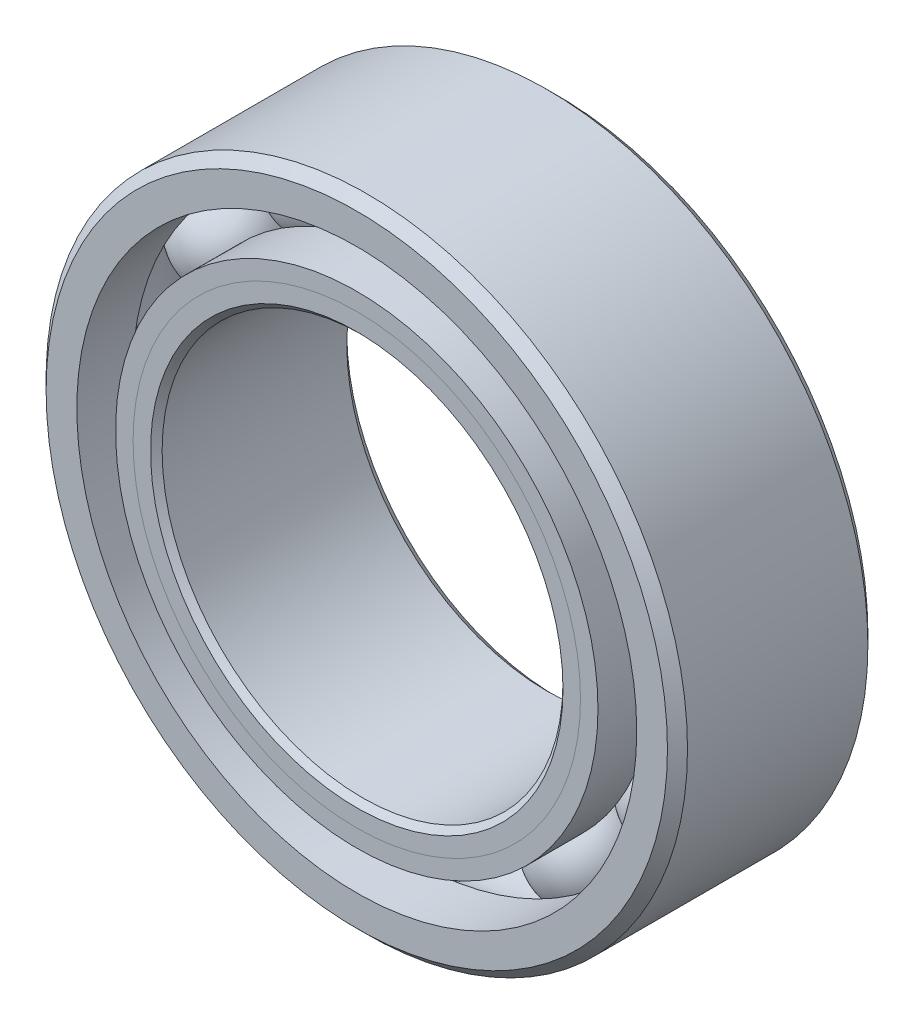
SolidWorks part; units mm, degrees
ref_plane "Front Plane" through (0, 0, 0) normal (0, 0, 1) x (1, 0, 0)
ref_plane "Top Plane" through (0, 0, 0) normal (0, 1, 0) x (1, 0, 0)
ref_plane "Right Plane" through (0, 0, 0) normal (1, 0, 0) x (0, 0, -1)
sketch "Sketch1" plane through (0, 0, 0) normal (1, 0, 0) x (0, 0, -1)
  line L0 (-1.9844, 0) -> (1.9844, 0) construction
  line L1 (0, 6.35) -> (0, -6.35) construction
  line L2 (1.7859, 6.35) -> (-1.7859, 6.35)
  line L3 (-1.7859, 6.35) -> (-1.9844, 6.1516)
  line L4 (-1.9844, 6.1516) -> (-1.9844, 5.5432)
  line L5 (-1.9844, 5.5432) -> (-0.8819, 5.5432)
  line L6 (1.9844, 5.5432) -> (0.8819, 5.5432)
  line L7 (1.9844, 6.1516) -> (1.9844, 5.5432)
  line L8 (1.7859, 6.35) -> (1.9844, 6.1516)
  line L9 (0, 6.35) -> (0, 5.1594) construction
  line L10 (0, 5.1594) -> (0, 3.9688) construction
  arc A0 (-0.8819, 5.5432) -> (0.8819, 5.5432) centre (0, 5.1594) cw
  point P14 (0, 3.9688)
  dimension "Width" = 3.9688
  dimension "OD" = 12.7
  dimension "D1" = 45
  dimension "D2" = 0.1984
  dimension "D3" = 1.7639
  dimension "D4" = 0.3838
revolve "Revolve1" add sketch "Sketch1" angle 360 about L0
sketch "Sketch2" plane through (0, 0, 0) normal (1, 0, 0) x (0, 0, -1)
  line L0 (-1.9844, 4.7756) -> (-0.8819, 4.7756)
  line L1 (-1.9844, 6.1516) -> (-1.9844, -6.1516) construction
  line L2 (-1.9844, 4.7756) -> (-1.9844, 4.4294)
  line L3 (-1.9844, 4.4294) -> (-1.6382, 4.0831)
  line L4 (-1.6382, 4.0831) -> (0, 4.0831)
  line L5 (0, 6.35) -> (0, -6.35) construction
  line L6 (0, 4.0831) -> (0, 4.1975)
  line L7 (0, 4.1975) -> (0, 3.9688) construction
  line L8 (-1.9844, 4.7756) -> (-1.9844, 4.0831) construction
  line L9 (-1.9844, 4.0831) -> (-1.6382, 4.0831) construction
  arc A0 (-0.8819, 4.7756) -> (0, 4.1975) centre (0, 5.1594) ccw
  arc A1 (0.8819, 5.5432) -> (-0.8819, 5.5432) centre (0, 5.1594) ccw construction
  circle A2 centre (0, 5.1594) radius 0.9618 construction
  dimension "D1" = 45
revolve "Revolve2" add sketch "Sketch2" angle 360 about L0
sketch "Sketch3" plane through (0, 0, 0) normal (1, 0, 0) x (0, 0, -1)
  line L0 (-1.9844, 4.4294) -> (-1.6382, 4.0831)
  line L1 (-1.6382, 4.0831) -> (0, 4.0831)
  line L2 (0, 4.0831) -> (0, 4.1975)
  line L3 (-1.9844, 4.4294) -> (-1.9844, 4.0831)
  line L4 (-1.9844, 4.7756) -> (-1.9844, 4.0831) construction
  line L5 (-1.9844, 4.0831) -> (-1.87, 3.9688)
  line L6 (-1.87, 3.9688) -> (1.7859, 3.9688)
  line L7 (1.7859, 6.35) -> (1.7859, -6.35) construction
  line L8 (1.7859, 3.9688) -> (1.9844, 4.1672)
  line L9 (1.9844, -6.1516) -> (1.9844, 6.1516) construction
  line L10 (1.9844, 4.1672) -> (1.9844, 4.7756)
  line L11 (1.9844, 4.7756) -> (0.8819, 4.7756)
  line L13 (1.7859, 6.35) -> (1.9844, 6.1516) construction
  circle A0 centre (0, 5.1594) radius 0.9618 construction
  arc A1 (0.8819, 4.7756) -> (0, 4.1975) centre (0, 5.1594) cw
revolve "Revolve3" add sketch "Sketch3" angle 360 about L0
sketch "Sketch4" plane through (0, 0, 0) normal (1, 0, 0) x (0, 0, -1)
  line L0 (-0.9618, 5.1594) -> (0.9618, 5.1594)
  circle A1 centre (0, 5.1594) radius 0.9618 construction
  arc A2 (-0.9618, 5.1594) -> (0.9618, 5.1594) centre (0, 5.1594) cw
  arc A3 (0.8819, 5.5432) -> (-0.8819, 5.5432) centre (0, 5.1594) ccw construction
revolve "Revolve4" add sketch "Sketch4" angle 360 about L0
ref_axis "Axis1" through (0, 0, -1.9844) along (0, 0, 1)
pattern_circular "CirPattern1" count 12 every 30 about axis through (0, 0, -1.9844) along (0, 0, 1) of bodies 104
equation "\"D2@Sketch1\" = \"Width@Sketch1\"*.05"
equation "\"D3@Sketch1\" = \"Width@Sketch1\"/2.25"
equation "\"D4@Sketch1\" = (((\"OD@Sketch1\"-\"Width@Sketch1\")/2)/3.25)/3.5"
equation "\"D2@CirPattern1\" = 360/\"Balls@CirPattern1\""
